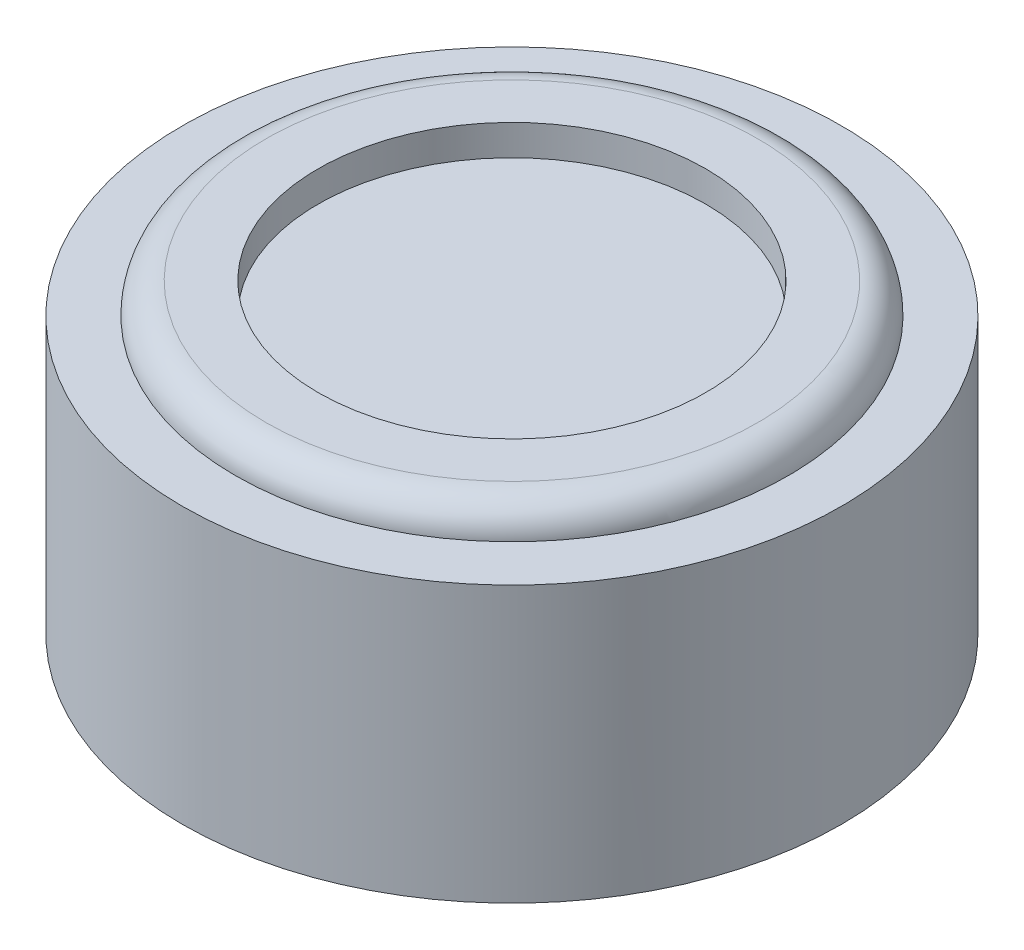
SolidWorks part; units mm, degrees
ref_plane "Front Plane" through (0, 0, 0) normal (0, 0, 1) x (1, 0, 0)
ref_plane "Top Plane" through (0, 0, 0) normal (0, 1, 0) x (1, 0, 0)
ref_plane "Right Plane" through (0, 0, 0) normal (1, 0, 0) x (0, 0, -1)
sketch "Sketch1" plane through (0, 0, 0) normal (0, 1, 0) x (1, 0, 0)
  circle A0 centre (0, 0) radius 16.15
  dimension "D1" = 32.3
extrude "Boss-Extrude1" add sketch "Sketch1" against normal blind 16.5
sketch "Sketch2" plane through (0, 0, 0) normal (0, 1, 0) x (1, 0, 0)
  circle A0 centre (0, 0) radius 13.55
  dimension "D1" = 27.1
extrude "Cut-Extrude1" cut sketch "Sketch2" against normal blind 1.5 flip side to cut
sketch "Sketch3" plane through (0, 0, 0) normal (0, 1, 0) x (1, 0, 0)
  circle A0 centre (0, 0) radius 9.5
  dimension "D1" = 19
extrude "Cut-Extrude2" cut sketch "Sketch3" against normal blind 1.5
ref_plane "Plane1" through (0, -16.5, 0) normal (0, -1, 0) x (-1, 0, 0)
sketch "Sketch4" plane through (0, -16.5, 0) normal (0, -1, 0) x (-1, 0, 0)
  circle A0 centre (0, 0) radius 13.55
  dimension "D1" = 27.1
extrude "Cut-Extrude3" cut sketch "Sketch4" against normal blind 1.5 flip side to cut
sketch "Sketch5" plane through (0, -16.5, 0) normal (0, -1, 0) x (-1, 0, 0)
  circle A0 centre (0, 0) radius 12
  dimension "D1" = 24
extrude "Cut-Extrude4" cut sketch "Sketch5" against normal blind 1.5
sketch "Sketch6" plane through (0, -16.5, 0) normal (0, -1, 0) x (-1, 0, 0)
  line L0 (0, 0) -> (0, 8.5) construction
  line L1 (0, 0) -> (6.0104, 6.0104) construction
  circle A0 centre (0, 0) radius 8.5 construction
  circle A1 centre (0, 8.5) radius 1.4
  circle A2 centre (6.0104, 6.0104) radius 1.4
  circle A3 centre (8.5, 0) radius 1.4 [skipped]
  circle A4 centre (6.0104, -6.0104) radius 1.4 [skipped]
  circle A6 centre (-6.0104, -6.0104) radius 1.4 [skipped]
  circle A7 centre (-8.5, 0) radius 1.4 [skipped]
  circle A8 centre (-6.0104, 6.0104) radius 1.4
  circle A10 centre (0, -8.5) radius 1.4
  circle A12 centre (0, -8.5) radius 1.4 [skipped]
  dimension "D1" = 17
  dimension "D2" = 2.8
  dimension "D4" = 45
  dimension "D3" = 8
extrude "Cut-Extrude7" cut sketch "Sketch6" against normal blind 2.5
fillet "Fillet2" radius 1.5 1 edges at (0, 0, 13.55)
